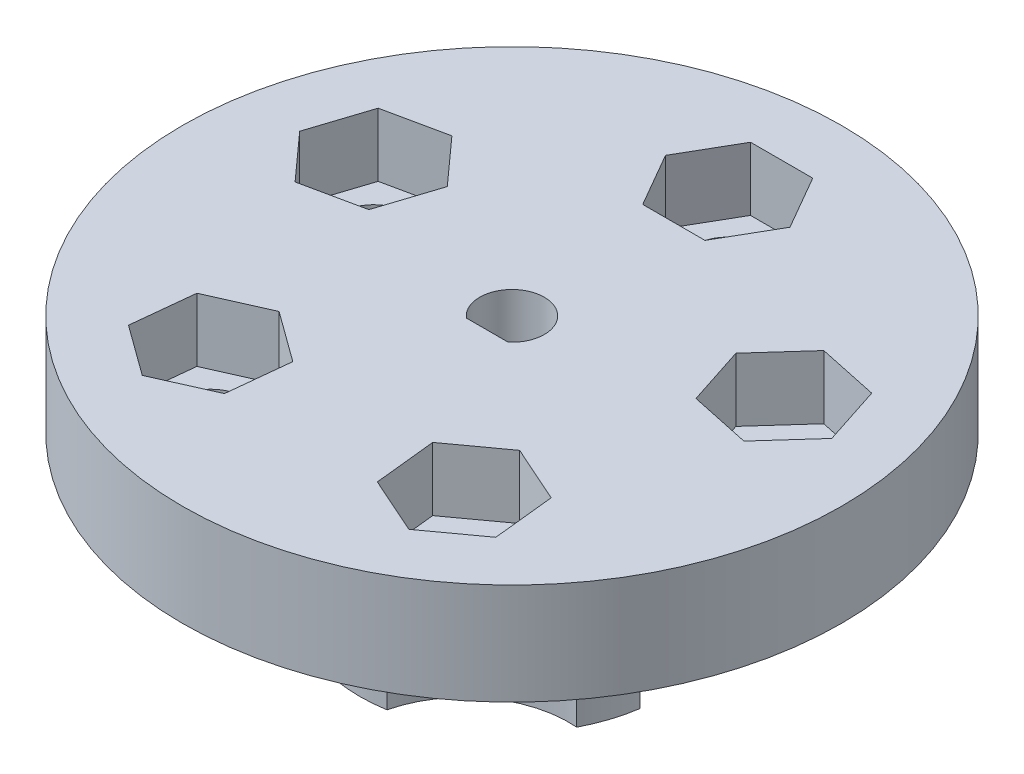
SolidWorks part; units mm, degrees
ref_plane "Front Plane" through (0, 0, 0) normal (0, 0, 1) x (1, 0, 0)
ref_plane "Top Plane" through (0, 0, 0) normal (0, 1, 0) x (1, 0, 0)
ref_plane "Right Plane" through (0, 0, 0) normal (1, 0, 0) x (0, 0, -1)
sketch "Sketch1" plane through (0, 0, 0) normal (0, 1, 0) x (1, 0, 0)
  line L1 (10, -13.7638) -> (16.1803, 5.2573) construction
  line L2 (16.1803, 5.2573) -> (0, 17.013) construction
  line L3 (0, 17.013) -> (-16.1803, 5.2573) construction
  line L4 (-16.1803, 5.2573) -> (-10, -13.7638) construction
  line L5 (-10, -13.7638) -> (10, -13.7638) construction
  circle A0 centre (0, 0) radius 13.7638 construction
  circle A15 centre (0, 0) radius 25.013 construction
  circle A16 centre (0, 17.013) radius 8 construction
  circle A17 centre (16.1803, 5.2573) radius 8 construction
  circle A18 centre (10, -13.7638) radius 8 construction
  circle A19 centre (-10, -13.7638) radius 8 construction
  circle A22 centre (-16.1803, 5.2573) radius 8 construction
  circle A23 centre (0, 0) radius 26
  circle A24 centre (0, 17.013) radius 2.65
  circle A25 centre (-16.1803, 5.2573) radius 2.65
  circle A26 centre (-10, -13.7638) radius 2.65
  circle A27 centre (10, -13.7638) radius 2.65
  circle A28 centre (16.1803, 5.2573) radius 2.65
  dimension "D1" = 16
  dimension "D2" = 20
  dimension "D3" = 52
  dimension "D4" = 5.3
extrude "Boss-Extrude1" add sketch "Sketch1" along normal blind 8
sketch "Sketch2" plane through (0, 8, 0) normal (0, 1, 0) x (1, 0, 0)
  line L0 (-12.1383, 3.944) -> (0, 0) construction
  line L1 (-11.3801, 6.2776) -> (-14.6638, 9.9246)
  line L2 (-14.6638, 9.9246) -> (-19.4641, 8.9043)
  line L3 (-19.4641, 8.9043) -> (-20.9806, 4.237)
  line L4 (-20.9806, 4.237) -> (-17.6968, 0.59)
  line L5 (-17.6968, 0.59) -> (-12.8966, 1.6103)
  line L6 (-12.8966, 1.6103) -> (-11.3801, 6.2776)
  line L7 (4.9075, 17.013) -> (2.4537, 21.263)
  line L8 (2.4537, 21.263) -> (-2.4537, 21.263)
  line L9 (-2.4537, 21.263) -> (-4.9075, 17.013)
  line L10 (-4.9075, 17.013) -> (-2.4537, 12.763)
  line L11 (-2.4537, 12.763) -> (2.4537, 12.763)
  line L12 (2.4537, 12.763) -> (4.9075, 17.013)
  line L13 (17.6968, 0.59) -> (20.9806, 4.237)
  line L14 (20.9806, 4.237) -> (19.4641, 8.9043)
  line L15 (19.4641, 8.9043) -> (14.6638, 9.9246)
  line L16 (14.6638, 9.9246) -> (11.3801, 6.2776)
  line L17 (11.3801, 6.2776) -> (12.8966, 1.6103)
  line L18 (12.8966, 1.6103) -> (17.6968, 0.59)
  line L19 (6.0298, -16.6484) -> (10.513, -18.6444)
  line L20 (10.513, -18.6444) -> (14.4832, -15.7599)
  line L21 (14.4832, -15.7599) -> (13.9702, -10.8793)
  line L22 (13.9702, -10.8793) -> (9.487, -8.8832)
  line L23 (9.487, -8.8832) -> (5.5168, -11.7678)
  line L24 (5.5168, -11.7678) -> (6.0298, -16.6484)
  line L25 (-13.9702, -10.8793) -> (-14.4832, -15.7599)
  line L26 (-14.4832, -15.7599) -> (-10.513, -18.6444)
  line L27 (-10.513, -18.6444) -> (-6.0298, -16.6484)
  line L28 (-6.0298, -16.6484) -> (-5.5168, -11.7678)
  line L29 (-5.5168, -11.7678) -> (-9.487, -8.8832)
  line L30 (-9.487, -8.8832) -> (-13.9702, -10.8793)
  circle A5 centre (-16.1803, 5.2573) radius 4.25 construction
  point P39 (0, 0)
  dimension "D1" = 8.5
  dimension "D2" = 5
extrude "Cut-Extrude1" cut sketch "Sketch2" against normal blind 5
sketch "Sketch3" plane through (0, 0, 0) normal (0, -1, 0) x (1, 0, 0)
  line L0 (-1.6432, 1.95) -> (1.6432, 1.95)
  arc A0 (-1.6432, 1.95) -> (1.6432, 1.95) centre (0, 0) ccw
  point P1 (0, -2.55)
  point P5 (-1.6497, -1.9555)
  point P6 (-1.942, 1.6337)
  point P7 (1.6387, 1.9463)
  dimension "D1" = 2.55
  dimension "D2" = 4.5
extrude "Cut-Extrude2" cut sketch "Sketch3" against normal through all
sketch "Sketch4" plane through (0, 0, 0) normal (0, -1, 0) x (1, 0, 0)
  line L0 (1.6432, 1.95) -> (-1.6432, 1.95) construction
  line L1 (1.6432, 1.95) -> (-1.6432, 1.95)
  arc A0 (-1.6432, 1.95) -> (1.6432, 1.95) centre (0, 0) ccw construction
  arc A1 (-10.6451, 5.5391) -> (-11.8679, 1.7758) centre (0, 0) ccw
  arc A3 (-1.6432, 1.95) -> (1.6432, 1.95) centre (0, 0) ccw
  arc A4 (1.9785, 11.8358) -> (10.6451, 5.5391) centre (10, 13.7638) ccw
  arc A5 (11.8679, 1.7758) -> (8.5575, -8.4124) centre (16.1803, -5.2573) ccw
  arc A6 (5.3563, -10.7383) -> (-5.3563, -10.7383) centre (0, -17.013) ccw
  arc A7 (-8.5575, -8.4124) -> (-11.8679, 1.7758) centre (-16.1803, -5.2573) ccw
  arc A8 (-10.6451, 5.5391) -> (-1.9785, 11.8358) centre (-10, 13.7638) ccw
  arc A9 (1.9785, 11.8358) -> (-1.9785, 11.8358) centre (0, 0) ccw
  arc A10 (11.8679, 1.7758) -> (10.6451, 5.5391) centre (0, 0) ccw
  arc A11 (5.3563, -10.7383) -> (8.5575, -8.4124) centre (0, 0) ccw
  arc A12 (-8.5575, -8.4124) -> (-5.3563, -10.7383) centre (0, 0) ccw
  dimension "D1" = 16.5
  dimension "D2" = 24
extrude "Boss-Extrude2" add sketch "Sketch4" along normal blind 12
sketch "Sketch5" plane through (0, 0, 0) normal (0, 0, 1) x (1, 0, 0)
  line L0 (0, -12) -> (0, 0) construction
  line L3 (-1.9785, -12) -> (1.9785, -12) construction
  circle A0 centre (0, -6) radius 1.75
  dimension "D1" = 3.5
extrude "Cut-Extrude3" cut sketch "Sketch5" along normal through all
ref_plane "Plane1" through (0, 0, 7.5) normal (0, 0, 1) x (1, 0, 0)
sketch "Sketch6" plane through (0, 0, 7.5) normal (0, 0, 1) x (1, 0, 0)
  circle A0 centre (0, -6) radius 2.75
  dimension "D1" = 5.5
extrude "Cut-Extrude4" cut sketch "Sketch6" along normal through all
sketch "Sketch7" plane through (0, -12, 0) normal (0, -1, 0) x (1, 0, 0)
  line L0 (1.6432, 1.95) -> (-1.6432, 1.95) construction
  line L1 (-3.1, 6.45) -> (3.1, 6.45)
  line L2 (-3.1, 6.45) -> (-3.1, 3.95)
  line L3 (-3.1, 3.95) -> (3.1, 3.95)
  line L4 (3.1, 6.45) -> (3.1, 3.95)
  line L5 (-3.1, 6.45) -> (3.1, 3.95) construction
  line L6 (-3.1, 3.95) -> (3.1, 6.45) construction
  point P0 (0, 5.2)
  point P5 (0, 0)
  point P6 (0, 0)
  dimension "D1" = 2.5
  dimension "D2" = 6.2
  dimension "D3" = 2
extrude "Cut-Extrude5" cut sketch "Sketch7" against normal blind 10
